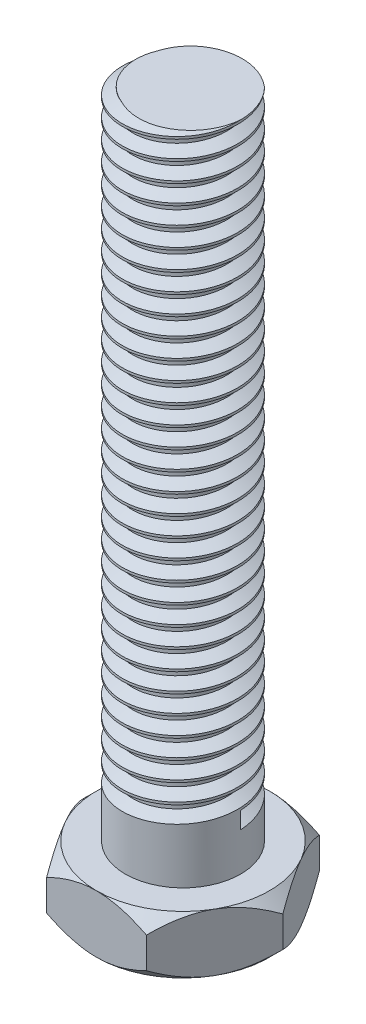
SolidWorks part; units mm, degrees
ref_plane "Front Plane" through (0, 0, 0) normal (0, 0, 1) x (1, 0, 0)
ref_plane "Top Plane" through (0, 0, 0) normal (0, 1, 0) x (1, 0, 0)
ref_plane "Right Plane" through (0, 0, 0) normal (1, 0, 0) x (0, 0, -1)
sketch "Sketch1" plane through (0, 0, 0) normal (0, 1, 0) x (1, 0, 0)
  line L1 (2.5981, 0) -> (1.299, 2.25)
  line L2 (1.299, 2.25) -> (-1.299, 2.25)
  line L3 (-1.299, 2.25) -> (-2.5981, 0)
  line L4 (-2.5981, 0) -> (-1.299, -2.25)
  line L5 (-1.299, -2.25) -> (1.299, -2.25)
  line L6 (1.299, -2.25) -> (2.5981, 0)
  circle A1 centre (0, 0) radius 2.25 construction
  dimension "D1" = 4.5
extrude "Boss-Extrude1" add sketch "Sketch1" along normal mid plane 1.5
sketch "Sketch2" plane through (0, 0.75, 0) normal (0, 1, 0) x (1, 0, 0)
  line L0 (1.299, 2.25) -> (-1.299, 2.25) construction
  circle A0 centre (0, 0) radius 2.25
extrude "Cut-Extrude2" cut sketch "Sketch2" against normal through all draft 45 flip side to cut
mirror "Mirror1" about plane through (0, 0, 0) normal (0, 1, 0) of "Cut-Extrude2" second plane through (0, 0, 0) second plane normal (0, 0, 1)
sketch "Sketch3" plane through (0, 0.75, 0) normal (0, 1, 0) x (1, 0, 0)
  circle A0 centre (0, 0) radius 1.5
  dimension "D1" = 3
extrude "Boss-Extrude2" add sketch "Sketch3" along normal blind 17
thread "Thread1" pitch 0.5 method cut profile "Thread Profile1" start angle 0, offset 1, length 0, pitch 0.5, diameter 3
ref_plane "Plane1" through (1.5, 1.75, 0) normal (0, 0, 1) x (1, 0, 0)
sketch "Thread Profile1" plane through (1.5, 1.75, 0) normal (0, 0, 1) x (1, 0, 0)
  line L0 (0, 0) -> (0, 0.5) construction
  line L11 (0, 0) -> (0, 0.4375)
  line L12 (0, 0.4375) -> (-0.2706, 0.2812)
  line L13 (-0.2706, 0.2812) -> (-0.2706, 0.1562)
  line L15 (-0.2706, 0.1562) -> (0, 0)
  line L17 (-0.2706, 0.2187) -> (0, 0.2187) construction
  point P2 (0, 0)
  dimension "Pitch" = 0.5
  dimension "Profile_Angle" = 60
  dimension "Profile_Land" = 0.125
  dimension "Profile_Height" = 0.2706
equation "\"Bolt shaft dia\"= 3mm"
equation "\"bolt head dia\"= 4.5mm"
equation "\"bolt head thickness\"= 1.5mm"
equation "\"Bolt shaft length\" = 17mm"
equation "\"D1@Sketch1\"=\"bolt head dia\""
equation "\"D1@Boss-Extrude1\"=\"bolt head thickness\""
equation "\"D1@Sketch3\"=\"Bolt shaft dia\""
equation "\"D1@Boss-Extrude2\"=\"Bolt shaft length\""
